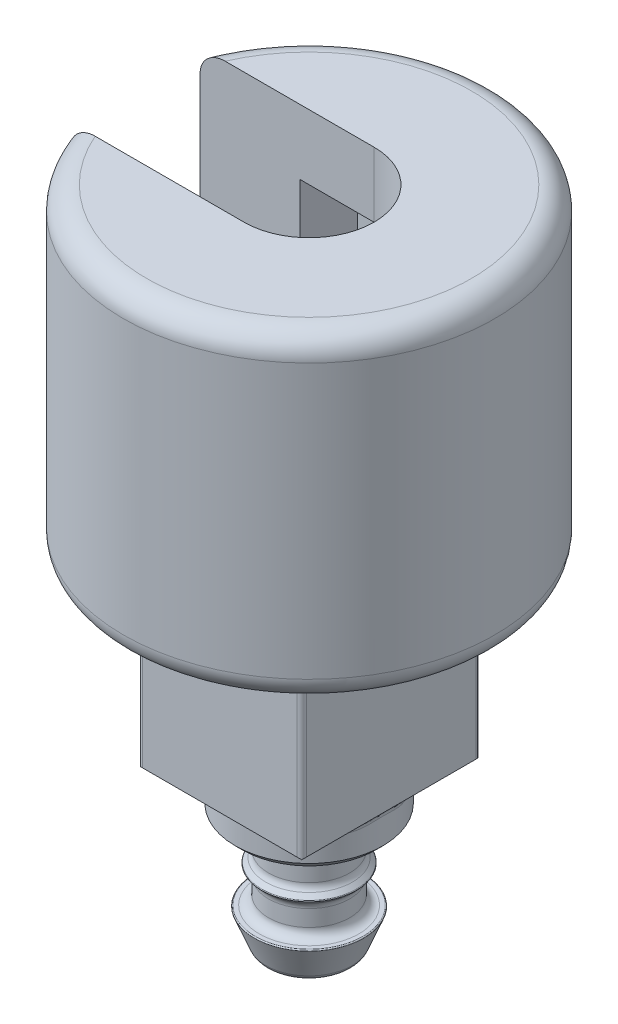
SolidWorks part; units mm, degrees
ref_plane "Front Plane" through (0, 0, 0) normal (0, 0, 1) x (1, 0, 0)
ref_plane "Top Plane" through (0, 0, 0) normal (0, 1, 0) x (1, 0, 0)
ref_plane "Right Plane" through (0, 0, 0) normal (1, 0, 0) x (0, 0, -1)
sketch "Sketch1" plane through (0, 0, 0) normal (0, 0, 1) x (1, 0, 0)
  line L0 (0, 1017.6623) -> (0, 12.7) construction
  line L1 (0, -12.7) -> (4.3656, -12.7)
  line L3 (4.3656, 0) -> (7.9375, 0)
  line L4 (7.9375, 0) -> (7.9375, 3.9688)
  line L8 (0, 3.9688) -> (0, -12.7)
  line L9 (4.3656, -12.7) -> (5.9531, -8.7312)
  line L22 (7.9375, 0) -> (7.9375, 3.9688) construction
  line L25 (7.9375, 6.35) -> (0, 6.35) construction
  line L27 (6.35, 3.9688) -> (7.9375, 3.9688)
  line L32 (5.9531, -8.7312) -> (4.3656, -8.7312)
  line L33 (4.3656, -8.7312) -> (4.3656, -5.5563)
  line L34 (4.3656, -3.9687) -> (5.1594, -4.7625)
  line L35 (5.1594, -4.7625) -> (4.3656, -5.5563)
  line L36 (5.1594, -4.7625) -> (4.3656, -4.7625) construction
  line L37 (4.3656, -3.9687) -> (4.3656, 0)
  line L38 (6.35, 3.9688) -> (0, 3.9688)
  line L40 (0, 3.9688) -> (0, -7.7377) construction
  dimension "D7" = 1.5875
  dimension "D1" = 12.7
  dimension "D2" = 3.9688
  dimension "D6" = 15.875
  dimension "D8" = 8.7312
  dimension "D10" = 7.9375
  dimension "D11" = 45
  dimension "D9" = 0.7937
revolve "Revolve1" add sketch "Sketch1" angle 360 about L0
fillet "Fillet3" radius 1 5 edges at (0, -12.7, 4.3656) (0, -8.7313, 4.3656) (0, 0, 4.3656) (0, -3.9688, 4.3656) (0, -5.5562, 4.3656)
fillet "Fillet4" radius 0.0992 2 edges at (0, -8.7313, 5.9531) (0, -4.7625, 5.1594)
ref_plane "Plane1" through (0, 3.9688, 0) normal (0, 1, 0) x (1, 0, 0)
sketch "Sketch2" plane through (0, 3.9688, 0) normal (0, 1, 0) x (1, 0, 0)
  line L0 (0, 9.6273) -> (0, -9.6273) construction
  line L9 (9.0227, 0) -> (-9.0227, 0) construction
  line L11 (8.8366, 9.6273) -> (-8.8366, 9.6273)
  line L12 (8.8366, 9.6273) -> (8.8366, -9.6273)
  line L13 (8.8366, -9.6273) -> (-8.8366, -9.6273)
  line L14 (-8.8366, 9.6273) -> (-8.8366, -9.6273)
  line L15 (8.8366, 9.6273) -> (-8.8366, -9.6273) construction
  line L16 (8.8366, -9.6273) -> (-8.8366, 9.6273) construction
  point P0 (0, 0)
  point P1 (0, 0)
  point P2 (0, 0)
  point P6 (0, 0)
  point P11 (0, 0)
extrude "Boss-Extrude1" add sketch "Sketch2" along normal blind 20
sketch "Sketch3" plane through (0, -12.7, 0) normal (0, -1, 0) x (1, 0, 0)
  circle A0 centre (0, 0) radius 2.413
extrude "Cut-Extrude1" cut sketch "Sketch3" against normal blind 29
sketch "Sketch5" plane through (0, 0, 0) normal (1, 0, 0) x (0, 0, -1)
  line L0 (0, 23.9688) -> (0, 3.9688) construction
  line L1 (9.6273, 23.9688) -> (-9.6273, 23.9688) construction
  line L2 (55, 3.9688) -> (-55, 3.9688) construction
  circle A0 centre (0, 13.9688) radius 2.25
  dimension "D1" = 4.5
extrude "Cut-Extrude3" cut sketch "Sketch5" against normal blind 22.86
chamfer "Chamfer2" distance 0.762 angle 45 5 edges at (8.8366, 3.9688, 0) (0, 3.9688, -9.6273) (-8.8366, 3.9688, 0) (0, 3.9688, 9.6273) (0, 0, 7.9375)
fillet "Fillet6" radius 0.762 1 edges at (0, 3.9688, 7.9375)
sketch "Sketch7" plane through (0, 23.9688, 0) normal (0, 1, 0) x (1, 0, 0)
  circle A0 centre (0, 0) radius 20
  dimension "D1" = 40
extrude "Boss-Extrude2" add sketch "Sketch7" along normal blind 7.5
sketch "Sketch8" plane through (0, 31.4688, 0) normal (0, 1, 0) x (1, 0, 0)
  circle A0 centre (0, 0) radius 12.5
  circle A1 centre (0, 0) radius 20
  circle A2 centre (0, 0) radius 20
  dimension "D1" = 0
extrude "Boss-Extrude3" add sketch "Sketch8" along normal blind 12
ref_plane "Plane2" through (0, 43.4688, 0) normal (0, 1, 0) x (1, 0, 0)
sketch "Sketch9" plane through (0, 43.4688, 0) normal (0, 1, 0) x (1, 0, 0)
  circle A1 centre (0, 0) radius 20
  circle A2 centre (0, 0) radius 20
  dimension "D1" = 0
extrude "Boss-Extrude4" add sketch "Sketch9" along normal blind 15
sketch "Sketch10" plane through (0, 43.4688, 0) normal (0, 1, 0) x (1, 0, 0)
  line L1 (-6.5547, -10.1998) -> (5.556, -10.7764)
  line L2 (5.556, -10.7764) -> (12.1106, -0.5766)
  line L3 (12.1106, -0.5766) -> (6.5547, 10.1998)
  line L4 (6.5547, 10.1998) -> (-5.556, 10.7764)
  line L5 (-5.556, 10.7764) -> (-12.1106, 0.5766)
  line L6 (-12.1106, 0.5766) -> (-6.5547, -10.1998)
  circle A0 centre (0, 0) radius 10.5 construction
  dimension "D1" = 21
extrude "Cut-Extrude4" cut sketch "Sketch10" along normal blind 8
sketch "Sketch11" plane through (0, 0, 0) normal (1, 0, 0) x (0, 0, -1)
  line L0 (0, 58.4688) -> (0, 23.9688) construction
  line L1 (20, 58.4688) -> (-20, 58.4688) construction
  line L2 (-20, 23.9688) -> (20, 23.9688) construction
  line L3 (7, 43.4688) -> (12.5, 43.4688)
  line L5 (-7, 43.4688) -> (-7, 58.4688)
  line L6 (-7, 58.4688) -> (7, 58.4688)
  line L7 (7, 43.4688) -> (7, 58.4688)
  line L8 (-7, 43.4688) -> (7, 58.4688) construction
  line L9 (-7, 58.4688) -> (7, 43.4688) construction
  line L10 (-12.5, 33.4688) -> (12.5, 33.4688)
  line L11 (-12.5, 33.4688) -> (-12.5, 43.4688)
  line L12 (-12.5, 43.4688) -> (-7, 43.4688)
  line L13 (12.5, 33.4688) -> (12.5, 43.4688)
  line L14 (-12.5, 33.4688) -> (12.5, 43.4688) construction
  line L15 (-12.5, 43.4688) -> (12.5, 33.4688) construction
  point P6 (0, 50.9688)
  point P11 (0, 38.4688)
  dimension "D1" = 14
  dimension "D3" = 10
  dimension "D4" = 25
extrude "Cut-Extrude5" cut sketch "Sketch11" against normal through all
sketch "Sketch12" plane through (0, 58.4688, 0) normal (0, 1, 0) x (1, 0, 0)
  circle A0 centre (0, 0) radius 7
  dimension "D1" = 14
extrude "Cut-Extrude6" cut sketch "Sketch12" against normal blind 12 and the other way through all
fillet "Fillet7" radius 2.5 6 edges at (0, 23.9688, -9.6273) (8.8366, 23.9688, 0) (0, 23.9688, 9.6273) (20, 58.4687, 0) (-8.8366, 23.9688, 0) (0, 23.9688, 20)
fillet "Fillet8" radius 0.5 8 edges at (-9.5689, 23.2365, 10.3595) (9.5689, 23.2365, 10.3595) (9.5689, 23.2365, -10.3595) (-9.5689, 23.2365, -10.3595) (-8.8366, 13.0998, 9.6273) (8.8366, 13.0998, 9.6273) (8.8366, 13.0998, -9.6273) (-8.8366, 13.0998, -9.6273)
